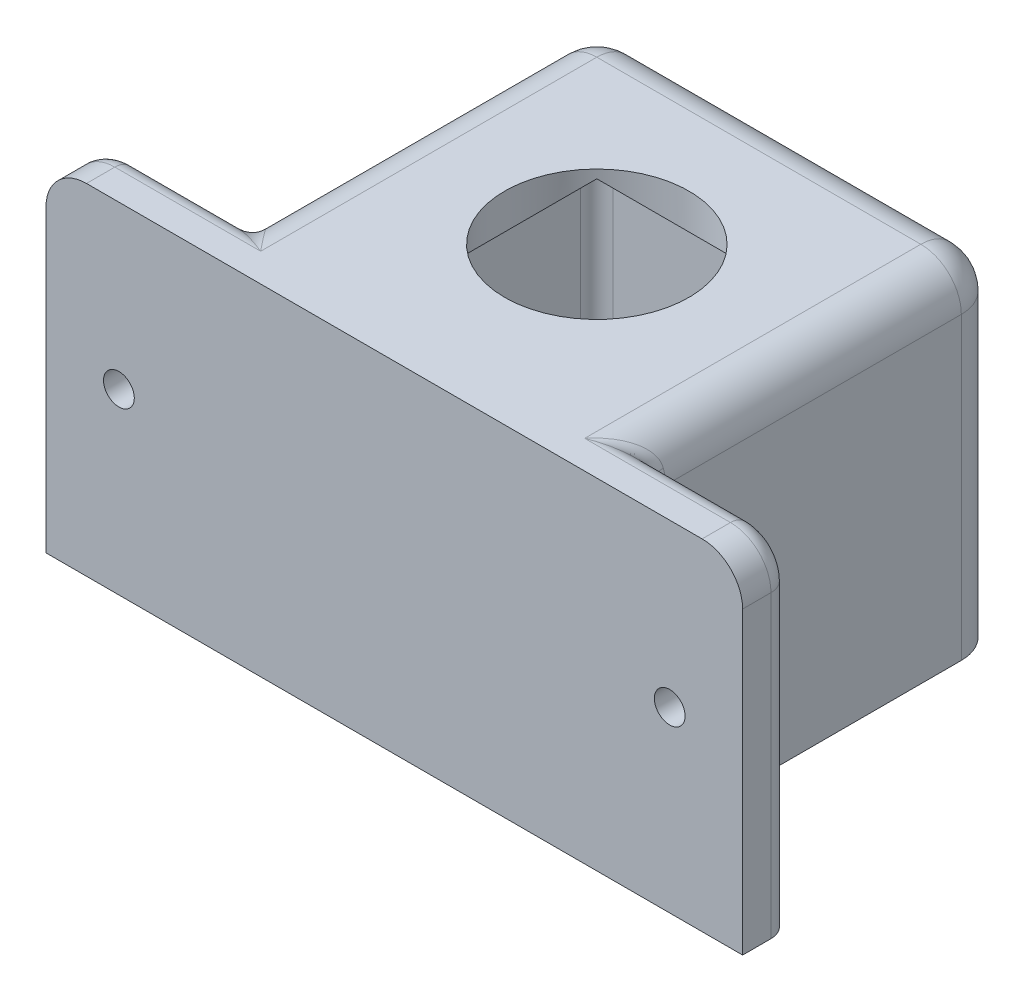
SolidWorks part; units mm, degrees
other "Interior Volume"
other "Stop Button Holder"
ref_plane "Front Plane" through (0, 0, 0) normal (0, 0, 1) x (1, 0, 0)
ref_plane "Top Plane" through (0, 0, 0) normal (0, 1, 0) x (1, 0, 0)
ref_plane "Right Plane" through (0, 0, 0) normal (1, 0, 0) x (0, 0, -1)
sketch "Half Body Sketch" plane through (0, 0, 0) normal (0, 1, 0) x (1, 0, 0)
  line L0 (0, 0) -> (0, 60.4502) construction
  line L1 (0, 50) -> (25, 50)
  line L2 (25, 50) -> (25, 6)
  line L3 (25, 6) -> (43, 6)
  line L4 (43, 6) -> (43, 0)
  line L5 (43, 0) -> (0, 0)
  line L6 (0, 50) -> (0, 0)
  dimension "D1" = 50
  dimension "D2" = 50
  dimension "D3" = 86
  dimension "D4" = 6
extrude "Half Body Extrude" add sketch "Half Body Sketch" along normal blind 42
mirror "Body Mirror" about plane through (0, 42, -50) normal (1, 0, 0) of bodies 101
fillet "Face Fillets" radius 5 5 edges at (-25, 42, -28) (-25, 21, -50) (25, 21, -50) (0, 42, -50) (25, 42, -28)
fillet "Corner Fillets" radius 5 2 edges at (43, 42, -3) (-43, 42, -3)
fillet "Wing Fillets" radius 2.5 6 edges at (-29, 42, -6) (-41.5355, 40.5355, -6) (29, 42, -6) (41.5355, 40.5355, -6) (-43, 18.5, -6) (43, 18.5, -6)
fillet "Transition Fillets" radius 2.5 6 edges at (22.4652, 41.35, -5.1815) (24.8296, 38.2941, -6) (-22.4652, 41.35, -5.1815) (-24.8296, 38.2941, -6) (25, 18.5, -6) (-25, 18.5, -6)
sketch "Interior Volume Sketch" plane through (0, 0, 0) normal (0, -1, 0) x (1, 0, 0)
  line L0 (25, -8.5) -> (25, -45) construction
  line L5 (-22, -3) -> (22, -3)
  line L6 (-22, -3) -> (-22, -47)
  line L7 (-22, -47) -> (22, -47)
  line L8 (22, -3) -> (22, -47)
  line L9 (20, -50) -> (-20, -50) construction
  line L10 (-25, -8.5) -> (-25, -45) construction
  line L11 (-43, 0) -> (43, 0) construction
  dimension "D1" = 3
  dimension "D2" = 3
  dimension "D3" = 3
  dimension "D4" = 3
extrude "Interior Volume Extrude" add sketch "Interior Volume Sketch" against normal offset from surface (38 mm away) 1 from offset 3 separate body up to face at (0, 42, -13) offset against normal yes
chamfer "Interior Volume Chamfer" distance 14 angle 45 4 edges at (22, 41, -25) (0, 41, -47) (0, 41, -3) (-22, 41, -25)
fillet "Interior Volume Fillet" radius 2 4 edges at (-22, 15, -47) (22, 15, -47) (-22, 15, -3) (22, 15, -3)
combine bodies "Cut Interior From Body" operation type subtract main body 102 bodies to subtract 103
sketch "Button Hole Sketch" plane through (0, 42, 0) normal (0, 1, 0) x (1, 0, 0)
  line L0 (-38, 0) -> (38, 0) construction
  circle A0 centre (0, 25) radius 11.375
  dimension "D1" = 22.75
  dimension "D2" = 25
extrude "Button Hole Cut Out" cut sketch "Button Hole Sketch" against normal up to next
sketch "Nut Access Sketch" plane through (0, 0, 0) normal (0, -1, 0) x (1, 0, 0)
  line L1 (0, -9.9889) -> (-13, -17.4944)
  line L2 (-13, -17.4944) -> (-13, -32.5056)
  line L3 (-13, -32.5056) -> (0, -40.0111)
  line L4 (0, -40.0111) -> (13, -32.5056)
  line L5 (13, -32.5056) -> (13, -17.4944)
  line L6 (13, -17.4944) -> (0, -9.9889)
  circle A0 centre (0, -25) radius 13 construction
  dimension "D1" = 26
extrude "Nut Access Cut Out" cut sketch "Nut Access Sketch" against normal blind 37.6
sketch "Mounting Screws Position Sketch" plane through (0, 0, -6) normal (0, 0, -1) x (-1, 0, 0)
  line L0 (0, 0) -> (0, 47.5161) construction
  line L1 (40.5, 0) -> (27.5, 0) construction
  point P0 (-34, 22)
  point P1 (34, 22)
  dimension "D1" = 68
  dimension "D2" = 22
hole_wizard "No. 6 Mounting Screws" positions "SketchNo. 6 Mounting Position Screws" profile "No. 6 Mounting Screws Profile Sketch" countersink size "#6" standard "ANSI Inch" end condition through all
sketch "SketchNo. 6 Mounting Position Screws" plane through (0, 0, -6) normal (0, 0, -1) x (-1, 0, 0)
  point P0 (-34, 22)
  point P2 (34, 22)
  point P5 (0, 0)
sketch "No. 6 Mounting Screws Profile Sketch" plane through (34, 22, -6) normal (1, 0, 0) x (0, 1, 0)
  line L0 (0, 0) -> (0, 6)
  line L1 (0, 6) -> (1.8986, 6)
  line L2 (1.8986, 6) -> (1.8986, 1.892)
  line L3 (1.8986, 1.892) -> (3.5433, 0)
  line L5 (3.5433, 0) -> (0, 0)
  line L6 (-1.8986, 1.892) -> (-3.5433, 0) construction
  line L11 (0, -6.35) -> (0, 107.95) construction
  dimension "Thru Hole Dia." = 3.7973
  dimension "Thru Hole Depth" = 6
  dimension "Near C'Sink Dia." = 7.0866
  dimension "Near C'Sink Angle" = 82
hole_wizard "M4 Mounting Screws" [suppressed] positions "M4 Mounting Screws Position Sketch" profile "M4 Mounting ScrewsProfile Sketch" countersink size "M4" standard "ANSI Metric"
sketch3d "M4 Mounting Screws Position Sketch"
  point P0 (34, 22, -6)
  point P3 (-34, 22, -6)
sketch "M4 Mounting ScrewsProfile Sketch" plane through (34, 22, -6) normal (1, 0, 0) x (0, 1, 0)
  line L0 (0, 0) -> (0, 6)
  line L1 (0, 6) -> (2.25, 6)
  line L2 (2.25, 6) -> (2.25, 2.45)
  line L3 (2.25, 2.45) -> (4.7, 0)
  line L5 (4.7, 0) -> (0, 0)
  line L6 (-2.25, 2.45) -> (-4.7, 0) construction
  line L11 (0, -6.35) -> (0, 107.95) construction
  dimension "Thru Hole Dia." = 4.5
  dimension "Thru Hole Depth" = 6
  dimension "Near C'Sink Dia." = 9.4
  dimension "Near C'Sink Angle" = 90
